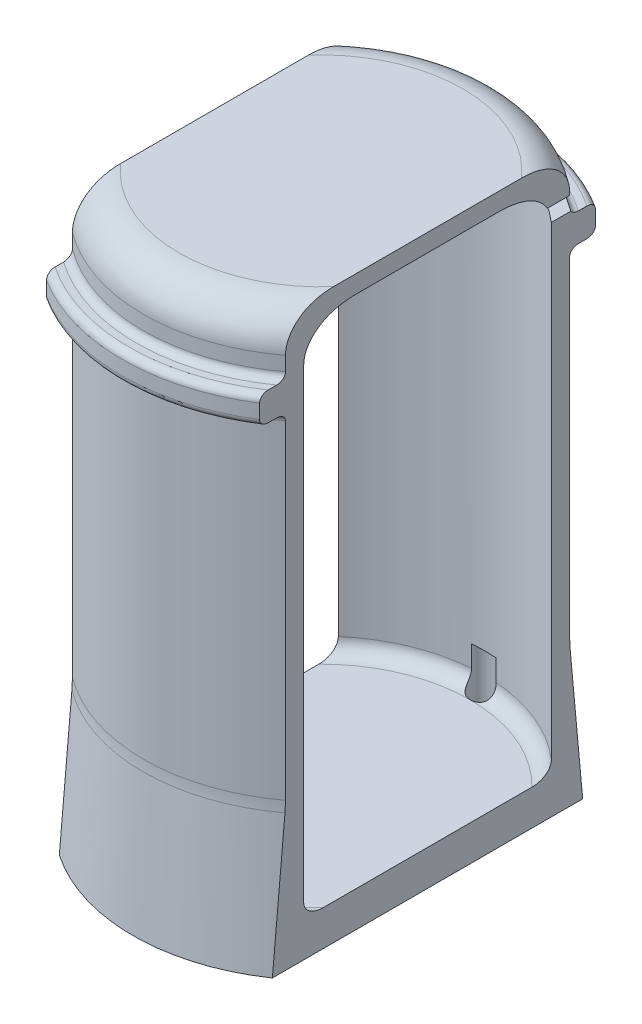
SolidWorks part; units mm, degrees
ref_plane "Front Plane" through (0, 0, 0) normal (0, 0, 1) x (1, 0, 0)
ref_plane "Top Plane" through (0, 0, 0) normal (0, 1, 0) x (1, 0, 0)
ref_plane "Right Plane" through (0, 0, 0) normal (1, 0, 0) x (0, 0, -1)
sketch "Sketch3" plane through (0, 0, 0) normal (0, 0, 1) x (1, 0, 0)
  line L0 (25, 68) -> (28, 68)
  line L1 (25, 0) -> (0, 0)
  line L2 (25, 0) -> (25, 68)
  line L3 (25, 80) -> (0, 80)
  line L4 (0, 0) -> (0, 80)
  line L5 (28, 68) -> (28, 72)
  line L6 (28, 72) -> (25, 72)
  line L7 (25, 72) -> (25, 80)
  dimension "D1" = 25
  dimension "D2" = 80
  dimension "D3" = 68
  dimension "D4" = 4
  dimension "D5" = 3
revolve "Revolve1" add sketch "Sketch3" angle 360 about L4
fillet "Fillet1" radius 5 1 edges at (0, 80, -25)
fillet "Fillet2" radius 1 4 edges at (0, 68, -25) (0, 72, -25) (0, 68, -28) (0, 72, -28)
sketch "Sketch11" plane through (0, 0, 0) normal (1, 0, 0) x (0, 0, -1)
  line L0 (0, 0) -> (0, 50000) construction
  line L1 (-25, 0) -> (-26.5, 0)
  line L2 (-26.5, 0) -> (-25, 20)
  line L3 (-25, 67) -> (-25, 0) construction
  line L4 (-25, 20) -> (-25, 0)
  dimension "D1" = 26.5
  dimension "D2" = 20
revolve "Revolve2" add sketch "Sketch11" angle 360 about L0
sketch "Sketch4" plane through (0, 0, 0) normal (0, 1, 0) x (1, 0, 0)
  line L1 (-15, 28) -> (15, 28)
  line L2 (-15, 28) -> (-15, -28)
  line L3 (-15, -28) -> (15, -28)
  line L4 (15, 28) -> (15, -28)
  circle A0 centre (0, 0) radius 28 construction
  dimension "D1" = 30
  dimension "D2" = 15
extrude "Cut-Extrude1" cut sketch "Sketch4" along normal through all flip side to cut
sketch "Sketch7" plane through (0, 0, 0) normal (1, 0, 0) x (0, 0, -1)
  line L0 (-21.8461, 0) -> (21.8461, 0) construction
  line L1 (0, 77.5) -> (18, 77.5)
  line L2 (0, 77.5) -> (0, 5)
  line L3 (0, 5) -> (23, 5)
  line L4 (23, 72.5) -> (23, 5)
  line L5 (0, 0) -> (0, 50000) construction
  line L6 (-13.2288, 80) -> (13.2288, 80) construction
  arc A0 (18, 77.5) -> (23, 72.5) centre (18, 72.5) cw
  point P11 (23, 77.5)
  dimension "D4" = 5
  dimension "D1" = 23
  dimension "D2" = 5
  dimension "D3" = 2.5
revolve "Cut-Revolve2" cut sketch "Sketch7" angle 360 about L5
fillet "Fillet5" radius 2 2 edges at (0, 5, 23) (0, 5, -23)
sketch "Sketch8" plane through (0, 0, 0) normal (0, -1, 0) x (1, 0, 0)
  line L0 (0, 0) -> (50000, 0) construction
  circle A0 centre (0, 22.75) radius 1.75
  circle A1 centre (0, -22.75) radius 1.75
  dimension "D1" = 3.5
  dimension "D2" = 22.75
extrude "Cut-Extrude2" cut sketch "Sketch8" against normal blind 10
sketch "Sketch9" plane through (0, 0, 0) normal (1, 0, 0) x (0, 0, -1)
  line L1 (16.8813, 74.5) -> (25.134, 74.5)
  line L2 (16.8813, 74.5) -> (16.8813, 72.5)
  line L3 (16.8813, 72.5) -> (25.134, 72.5)
  line L4 (25.134, 74.5) -> (25.134, 72.5)
  line L6 (27, 72) -> (22.4499, 72) construction
  arc A0 (25, 73) -> (26, 72) centre (26, 73) ccw construction
  spline S1 degree 3 poles (9.9499, 77.5) (10.7849, 77.5) (11.6119, 77.4372) (12.8337, 77.1959) (13.2407, 77.0897) (14.0296, 76.8192) (14.4111, 76.6556) (15.1428, 76.259) (15.4952, 76.0235) (15.9714, 75.6207) (16.1222, 75.4778) (16.4063, 75.1728) (16.5405, 75.0095) (16.9051, 74.4975) (17.0985, 74.1284) (17.3673, 73.3287) (17.4356, 72.9193) (17.4356, 72.5) knots 0 0 0 0 0.25 0.25 0.375 0.375 0.5 0.5 0.625 0.625 0.6875 0.6875 0.75 0.75 0.875 0.875 1 1 1 1 construction
  dimension "D1" = 0.5
  dimension "D2" = 2
extrude "Cut-Extrude3" cut sketch "Sketch9" against normal through all and the other way through all
fillet "Fillet6" radius 20 2 edges at (0, 20, 25) (0, 20, -25)
